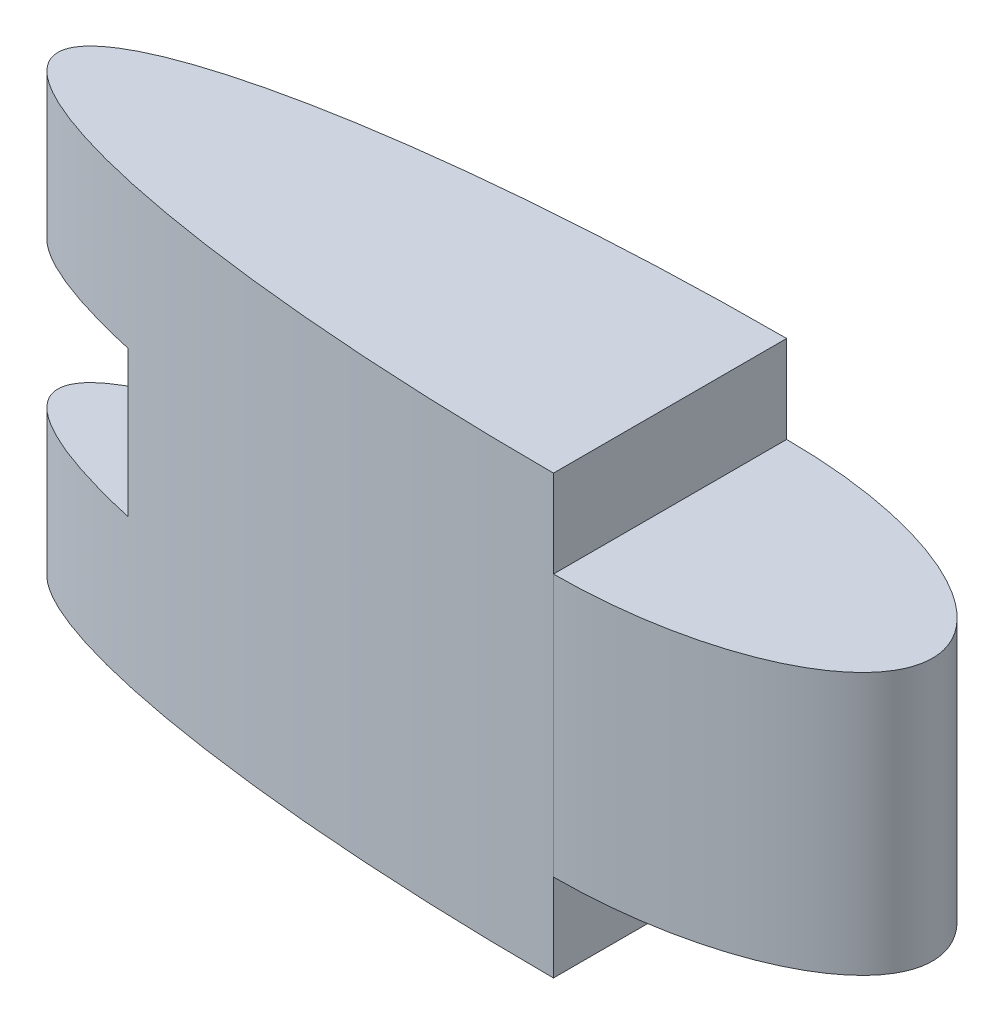
SolidWorks part; units mm, degrees
ref_plane "Alzado" through (0, 0, 0) normal (0, 0, 1) x (1, 0, 0)
ref_plane "Planta" through (0, 0, 0) normal (0, 1, 0) x (1, 0, 0)
ref_plane "Vista lateral" through (0, 0, 0) normal (1, 0, 0) x (0, 0, -1)
sketch "Sketch1" plane through (0, 0, 0) normal (0, 1, 0) x (1, 0, 0)
  line L3 (-210, 0) -> (210, 0) construction
  line L4 (-90, 0) -> (90, 0) construction
  ellipse E2 centre (0, 0) end of major axis (-90, 0) minor radius 40 (0, -40) -> (0, 40) ccw
  ellipse E3 centre (0, 0) end of major axis (210, 0) minor radius 40 (0, 40) -> (0, -40) ccw
  dimension "D5" = 80
  dimension "D6" = 210
  dimension "D7" = 90
extrude "Boss-Extrude1" add sketch "Sketch1" along normal blind 150
sketch "Sketch2" plane through (0, 0, 0) normal (0, 0, 1) x (1, 0, 0)
  line L0 (0, 0) -> (90, 0) construction
  point P4 (45, 0)
ref_axis "Axis1" through (45, 0, 0) along (0, -1, 0)
sketch "Sketch3" plane through (0, 0, 0) normal (0, 0, 1) x (1, 0, 0)
  line L0 (-210, 150) -> (-210, 0) construction
  line L1 (90, 150) -> (0, 150)
  line L2 (90, 150) -> (90, 120)
  line L3 (90, 120) -> (0, 120)
  line L4 (0, 150) -> (0, 120)
  line L5 (90, 0) -> (0, 0)
  line L6 (90, 0) -> (90, 30)
  line L7 (90, 30) -> (0, 30)
  line L8 (0, 0) -> (0, 30)
  line L9 (-210, 100) -> (-160, 100)
  line L10 (-210, 100) -> (-210, 50)
  line L11 (-210, 50) -> (-160, 50)
  line L12 (-160, 100) -> (-160, 50)
  line L13 (0, 150) -> (-210, 150) construction
  dimension "D1" = 90
  dimension "D2" = 30
  dimension "D3" = 30
  dimension "D4" = 90
  dimension "D5" = 50
  dimension "D6" = 50
  dimension "D7" = 50
extrude "Cut-Extrude1" cut sketch "Sketch3" against normal up to next and the other way up to next
sketch "Sketch4" plane through (0, 100, 0) normal (0, -1, 0) x (1, 0, 0)
  line L0 (0, 0) -> (-312.1296, 0) construction
  ellipse E0 centre (0, 0) end of major axis (210, 0) minor radius 40 (0, 40) -> (0, -40) ccw construction
  point P1 (-210, 0)
  point P2 (-185, 0)
  dimension "D1" = 25
ref_axis "Axis2" through (-185, 100, 0) along (0, -1, 0)
